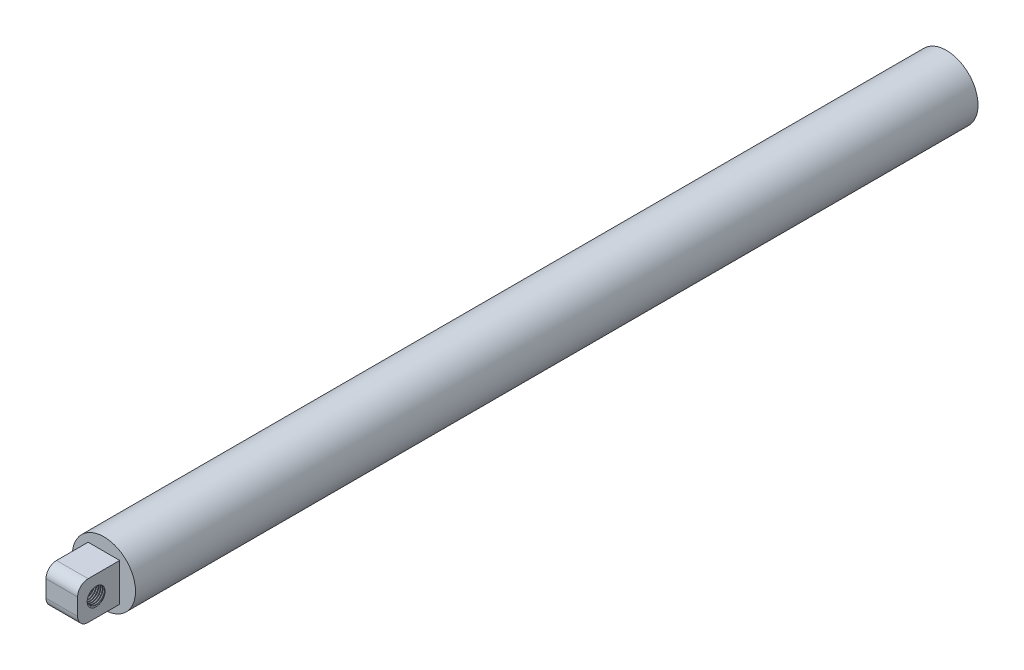
SolidWorks part; units mm, degrees
ref_plane "Front Plane" through (0, 0, 0) normal (0, 0, 1) x (1, 0, 0)
ref_plane "Top Plane" through (0, 0, 0) normal (0, 1, 0) x (1, 0, 0)
ref_plane "Right Plane" through (0, 0, 0) normal (1, 0, 0) x (0, 0, -1)
sketch "Sketch2" plane through (0, 0, 0) normal (0, 0, 1) x (1, 0, 0)
  circle A0 centre (0, 0) radius 15
  dimension "D1" = 30
extrude "Boss-Extrude1" add sketch "Sketch2" along normal blind 400
sketch "Sketch3" plane through (0, 0, 0) normal (0, 0, -1) x (-1, 0, 0)
  circle A0 centre (0, 0) radius 5
  dimension "D1" = 10
extrude "Cut-Extrude1" cut sketch "Sketch3" against normal blind 300
sketch "Sketch4" plane through (0, 0, 400) normal (0, 0, 1) x (1, 0, 0)
  line L1 (-7.5, 9) -> (7.5, 9)
  line L2 (-7.5, 9) -> (-7.5, -9)
  line L3 (-7.5, -9) -> (7.5, -9)
  line L4 (7.5, 9) -> (7.5, -9)
  line L5 (-7.5, 9) -> (7.5, -9) construction
  line L6 (-7.5, -9) -> (7.5, 9) construction
  point P0 (0, 0)
  dimension "D1" = 15
  dimension "D2" = 18
extrude "Boss-Extrude2" add sketch "Sketch4" along normal blind 20
sketch "Sketch5" plane through (7.5, 0, 0) normal (1, 0, 0) x (0, 0, -1)
  line L0 (-420, 0) -> (-400, 0) construction
  line L1 (-420, -9) -> (-420, 9) construction
  line L2 (-400, -9) -> (-400, 9) construction
  circle A0 centre (-411, 0) radius 4
  dimension "D1" = 8
  dimension "D2" = 9
extrude "Cut-Extrude2" cut sketch "Sketch5" against normal blind 15
thread "Thread1" pitch 1 method cut profile "Thread Profile1" start angle 0, offset 0, length 15, pitch 1, diameter 8
ref_plane "Plane1" through (-7.5, 0, 407) normal (0, -1, 0) x (0, 0, -1)
sketch "Thread Profile1" plane through (-7.5, 0, 407) normal (0, -1, 0) x (0, 0, -1)
  line L0 (0, 0) -> (0, 1) construction
  line L1 (0, 0) -> (0.5413, 0.3125)
  line L2 (0.5413, 0.3125) -> (0.5413, 0.4375)
  line L3 (0.5413, 0.4375) -> (0, 0.75)
  line L4 (0.5413, 0.375) -> (0, 0.375) construction
  line L11 (0, 0) -> (0, 0.75)
  point P2 (0, 0)
  dimension "Pitch" = 1
  dimension "Profile_Angle" = 60
  dimension "Profile_Land" = 0.125
  dimension "Profile_Height" = 0.5413
fillet "Fillet1" radius 5 2 edges at (0, -9, 420) (0, 9, 420)
